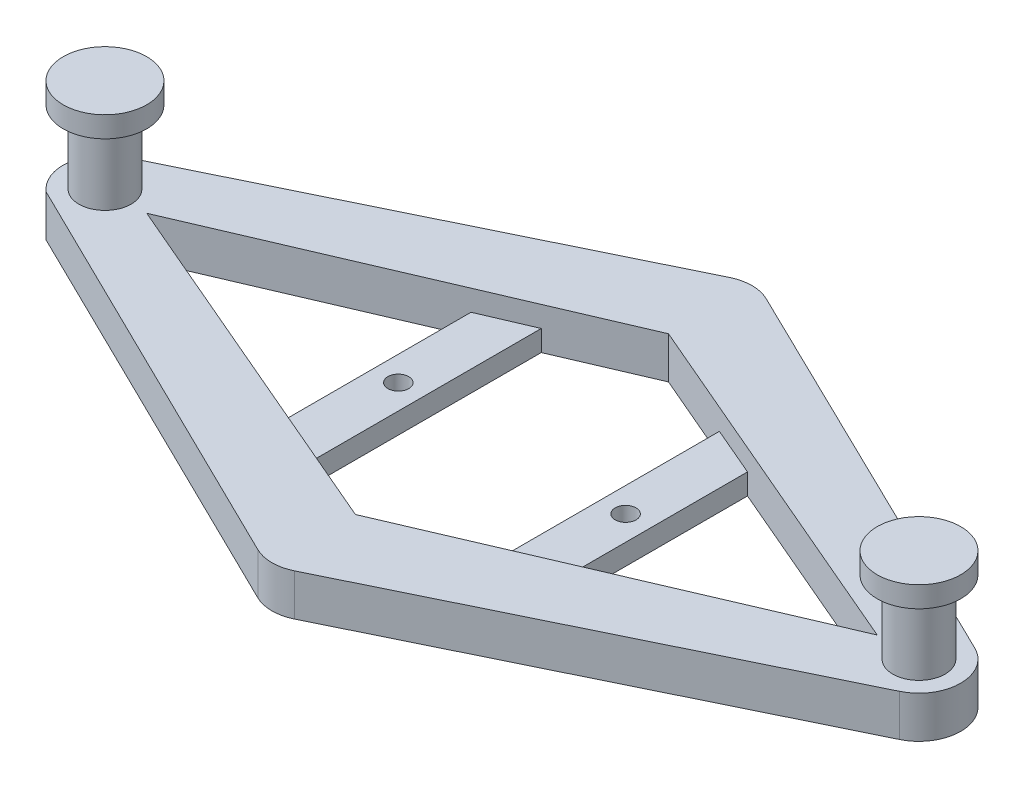
SolidWorks part; units mm, degrees
ref_plane "Front Plane" through (0, 0, 0) normal (0, 0, 1) x (1, 0, 0)
ref_plane "Top Plane" through (0, 0, 0) normal (0, 1, 0) x (1, 0, 0)
ref_plane "Right Plane" through (0, 0, 0) normal (1, 0, 0) x (0, 0, -1)
sketch "Base" plane through (0, 0, 0) normal (0, 1, 0) x (1, 0, 0)
  line L0 (0, 0) -> (49.53, 0)
  line L1 (0, 0) -> (-49.53, 0)
  line L2 (0, 0) -> (0, 24.13)
  line L3 (0, 0) -> (0, -24.13)
  line L4 (-44.45, 0) -> (0, 19.05)
  line L5 (0, 19.05) -> (44.45, 0)
  line L6 (44.45, 0) -> (0, -19.05)
  line L7 (0, -19.05) -> (-44.45, 0)
  line L8 (-51.7549, 4.5669) -> (-2.2249, 28.6969)
  line L9 (-52.8265, -3.8652) -> (-2.238, -28.6905)
  line L10 (2.2249, -28.6969) -> (51.7549, -4.5669)
  line L11 (51.7077, 4.5895) -> (2.2249, 28.6969)
  arc A0 (-51.7549, 4.5669) -> (-52.8265, -3.8652) centre (-49.53, 0) ccw
  arc A1 (2.2249, 28.6969) -> (-2.2249, 28.6969) centre (0, 24.13) ccw
  arc A2 (51.7549, -4.5669) -> (51.7077, 4.5895) centre (49.53, 0) ccw
  arc A3 (-2.238, -28.6905) -> (2.2249, -28.6969) centre (0, -24.13) ccw
  point P10 (0, 19.05)
  point P11 (-44.45, 0)
  point P12 (0, -19.05)
  point P13 (44.45, 0)
  point P27 (-51.7549, 4.5669)
  point P28 (-52.8265, -3.8652)
  point P29 (-2.238, -28.6905)
  point P30 (2.2249, -28.6969)
  point P31 (51.7549, -4.5669)
  point P32 (51.8018, 4.5437)
  point P33 (2.2249, 28.6969)
  point P34 (-2.2249, 28.6969)
sketch "Sketch4" plane through (0, 0, 0) normal (0, 1, 0) x (1, 0, 0)
  line L0 (-44.45, 0) -> (0, 19.05)
  line L1 (0, 19.05) -> (44.45, 0)
  line L2 (44.45, 0) -> (0, -19.05)
  line L3 (0, -19.05) -> (-44.45, 0)
  line L4 (-51.7549, 4.5669) -> (-2.2249, 28.6969)
  line L5 (-52.8265, -3.8652) -> (-2.238, -28.6905)
  line L6 (2.2249, -28.6969) -> (51.7549, -4.5669)
  line L7 (51.7077, 4.5895) -> (2.2249, 28.6969)
  arc A0 (-51.7549, 4.5669) -> (-52.8265, -3.8652) centre (-49.53, 0) ccw
  arc A1 (2.2249, 28.6969) -> (-2.2249, 28.6969) centre (0, 24.13) ccw
  arc A2 (51.7549, -4.5669) -> (51.7077, 4.5895) centre (49.53, 0) ccw
  arc A3 (-2.238, -28.6905) -> (2.2249, -28.6969) centre (0, -24.13) ccw
extrude "Boss-Extrude1" add sketch "Sketch4" along normal blind 5.08
sketch "Sketch5" plane through (0, 5.08, 0) normal (0, 1, 0) x (1, 0, 0)
  circle A0 centre (-49.53, 0) radius 3.175
  circle A1 centre (49.53, 0) radius 3.175
extrude "Boss-Extrude2" add sketch "Sketch5" along normal blind 8.89
sketch "Sketch8" plane through (0, 0, 0) normal (0, 1, 0) x (1, 0, 0)
  line L0 (-12.6059, 13.6475) -> (-12.6059, -13.6475)
  line L1 (-44.45, 0) -> (0, 19.05) construction
  line L2 (0, -19.05) -> (-44.45, 0) construction
  line L3 (-16.8237, 11.8398) -> (-16.8237, -11.8398)
  line L4 (0, 19.05) -> (0, -19.05)
  line L5 (12.6059, 13.6475) -> (12.6059, -13.6475)
  line L6 (16.8237, 11.8398) -> (16.8237, -11.8398)
  line L7 (-16.8237, 0) -> (-12.6059, 0)
  line L8 (12.6059, 0) -> (16.8237, 0)
  line L9 (-16.8237, 11.8398) -> (-12.6059, 13.6475)
  line L10 (-16.8237, -11.8398) -> (-12.6059, -13.6475)
  line L11 (12.6059, 13.6475) -> (16.8237, 11.8398)
  line L12 (12.6059, -13.6475) -> (16.8237, -11.8398)
  circle A0 centre (14.7148, 0) radius 1.27
  circle A1 centre (-14.7148, 0) radius 1.27
sketch "Sketch9" plane through (0, 0, 0) normal (0, 1, 0) x (1, 0, 0)
  line L0 (-10.839, 14.4047) -> (-10.839, -14.4047)
  line L1 (-16.8237, 11.8398) -> (-16.8237, -11.8398)
  line L4 (-16.8237, 11.8398) -> (-10.839, 14.4047)
  line L5 (-16.8237, -11.8398) -> (-10.839, -14.4047)
  line L8 (-44.45, 0) -> (0, 19.05) construction
  line L9 (0, -19.05) -> (-44.45, 0) construction
  line L10 (-16.8237, 0) -> (-10.839, 0)
  line L11 (0, 19.05) -> (0, -19.05)
  line L12 (16.8237, 11.8398) -> (10.839, 14.4047)
  line L13 (16.8237, -11.8398) -> (10.839, -14.4047)
  line L14 (16.8237, 11.8398) -> (16.8237, -11.8398)
  line L15 (10.839, 14.4047) -> (10.839, -14.4047)
  circle A2 centre (-13.8314, 0) radius 1.27
  circle A3 centre (13.8314, 0) radius 1.27
  point P8 (-13.8314, 13.1223)
  point P25 (13.8314, 13.1223)
sketch "Sketch11" plane through (0, 13.97, 0) normal (0, 1, 0) x (1, 0, 0)
  circle A0 centre (49.53, 0) radius 5.08
sketch "Sketch12" plane through (0, 13.97, 0) normal (0, 1, 0) x (1, 0, 0)
  circle A0 centre (49.53, 0) radius 5.08
extrude "Boss-Extrude4" add sketch "Sketch12" along normal blind 2.54
sketch "Sketch13" plane through (0, 13.97, 0) normal (0, 1, 0) x (1, 0, 0)
  circle A0 centre (-49.53, 0) radius 5.08
sketch "Sketch14" plane through (0, 13.97, 0) normal (0, 1, 0) x (1, 0, 0)
  circle A0 centre (-49.53, 0) radius 5.08
extrude "Boss-Extrude5" add sketch "Sketch14" along normal blind 2.54
sketch "Sketch15" plane through (0, 0, 0) normal (0, 1, 0) x (1, 0, 0)
  line L0 (-10.839, 14.4047) -> (-10.839, -14.4047)
  line L1 (-16.8237, 11.8398) -> (-16.8237, -11.8398)
  line L2 (-16.8237, 11.8398) -> (-10.839, 14.4047)
  line L3 (-16.8237, -11.8398) -> (-10.839, -14.4047)
  line L4 (16.8237, 11.8398) -> (10.839, 14.4047)
  line L5 (16.8237, -11.8398) -> (10.839, -14.4047)
  line L6 (16.8237, 11.8398) -> (16.8237, -11.8398)
  line L7 (10.839, 14.4047) -> (10.839, -14.4047)
  circle A0 centre (-13.8314, 0) radius 1.27
  circle A1 centre (13.8314, 0) radius 1.27
  point P4 (-10.839, 0)
  point P7 (-13.8314, 13.1223)
extrude "Boss-Extrude6" add sketch "Sketch15" along normal blind 2.54 separate body
